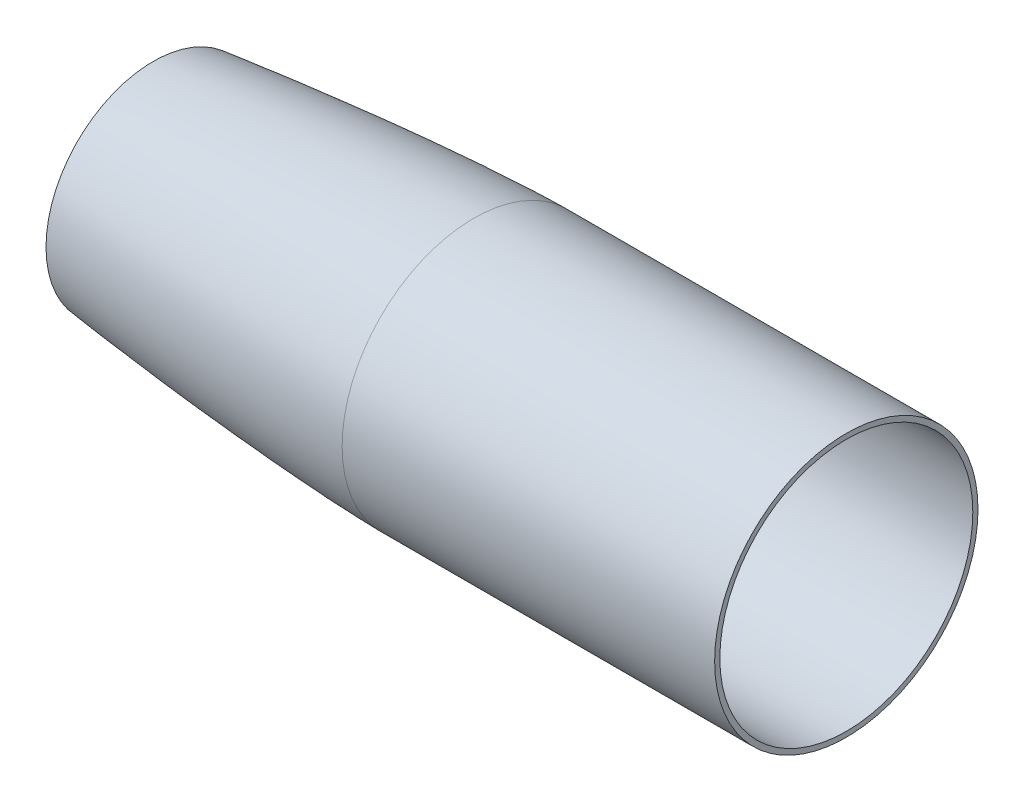
SolidWorks part; units mm, degrees
material "1060 Alloy"
ref_plane "Front Plane" through (0, 0, 0) normal (0, 0, 1) x (1, 0, 0)
ref_plane "Top Plane" through (0, 0, 0) normal (0, 1, 0) x (1, 0, 0)
ref_plane "Right Plane" through (0, 0, 0) normal (1, 0, 0) x (0, 0, -1)
sketch "Sketch2" plane through (0, 0, 0) normal (0, 0, 1) x (1, 0, 0)
  line L0 (0, 0) -> (5.418, 0)
  line L2 (0, 0) -> (553.8752, 0) construction
  line L3 (500, 76) -> (500, 73)
  line L4 (500, 76) -> (515, 76)
  line L5 (515, 76) -> (515, 73)
  line L6 (515, 73) -> (500, 73)
  spline S0 degree 4 poles (0, 0) (0.0035, 0.0138) (0.0132, 0.0403) (0.0421, 0.0896) (0.1033, 0.1748) (0.1957, 0.2791) (0.3129, 0.3945) (0.4445, 0.5113) (0.6264, 0.662) (0.9054, 0.8743) (1.3931, 1.2103) (2.2715, 1.7479) (3.8159, 2.5811) (6.6298, 3.9077) (11.7322, 5.9906) (20.2155, 8.9748) (31.7245, 12.4921) (45.6068, 16.2812) (64.6514, 21.0209) (87.6584, 26.2066) (114.7224, 31.7463) (145.854, 37.5379) (177.0669, 42.8718) (208.3451, 47.8072) (239.6781, 52.3812) (271.0588, 56.6152) (302.4822, 60.5197) (330.0118, 63.6484) (353.6316, 66.1189) (373.3295, 68.0301) (389.0964, 69.4668) (404.872, 70.8061) (418.6831, 71.887) (430.5264, 72.7427) (440.3994, 73.4044) (448.3, 73.9011) (455.2148, 74.3048) (461.1432, 74.6268) (466.0844, 74.8778) (470.0378, 75.0676) (476.0055, 75.3363) (481.7365, 75.5634) (487.2308, 75.7481) (492.4881, 75.8847) (495.117, 75.9403) (497.3706, 75.978) (498.8731, 75.9936) (499.6244, 76) (500, 76) knots 0 0 0 0 0 0.000112 0.000223 0.000447 0.000827 0.001207 0.00152 0.001832 0.002688 0.003968 0.006183 0.009943 0.016507 0.028468 0.049587 0.080772 0.111303 0.141834 0.204204 0.266574 0.328944 0.391314 0.453684 0.516055 0.578425 0.640795 0.703165 0.73435 0.765535 0.79672 0.827905 0.85909 0.874683 0.890275 0.905868 0.92146 0.929257 0.937053 0.944849 0.952645 0.976323 0.982242 0.988161 0.994081 0.99704 1 1 1 1 1 construction
  spline S1 degree 4 poles (0, 0) (0.0035, 0.0138) (0.0132, 0.0403) (0.0421, 0.0896) (0.1033, 0.1748) (0.1957, 0.2791) (0.3129, 0.3945) (0.4445, 0.5113) (0.6264, 0.662) (0.9054, 0.8743) (1.3931, 1.2103) (2.2715, 1.7479) (3.8159, 2.5811) (6.6298, 3.9077) (11.7322, 5.9906) (20.2155, 8.9748) (31.7245, 12.4921) (45.6068, 16.2812) (64.6514, 21.0209) (87.6584, 26.2066) (114.7224, 31.7463) (145.854, 37.5379) (177.0669, 42.8718) (208.3451, 47.8072) (239.6781, 52.3812) (271.0588, 56.6152) (302.4822, 60.5197) (330.0118, 63.6484) (353.6316, 66.1189) (373.3295, 68.0301) (389.0964, 69.4668) (404.872, 70.8061) (418.6831, 71.887) (430.5264, 72.7427) (440.3994, 73.4044) (448.3, 73.9011) (455.2148, 74.3048) (461.1432, 74.6268) (466.0844, 74.8778) (470.0378, 75.0676) (476.0055, 75.3363) (481.7365, 75.5634) (487.2308, 75.7481) (492.4881, 75.8847) (495.117, 75.9403) (497.3706, 75.978) (498.8731, 75.9936) (499.6244, 76) (500, 76) knots 0 0 0 0 0 0.000112 0.000223 0.000447 0.000827 0.001207 0.00152 0.001832 0.002688 0.003968 0.006183 0.009943 0.016507 0.028468 0.049587 0.080772 0.111303 0.141834 0.204204 0.266574 0.328944 0.391314 0.453684 0.516055 0.578425 0.640795 0.703165 0.73435 0.765535 0.79672 0.827905 0.85909 0.874683 0.890275 0.905868 0.92146 0.929257 0.937053 0.944849 0.952645 0.976323 0.982242 0.988161 0.994081 0.99704 1 1 1 1 1
  spline S2 degree 1 poles (2.4624, -1.7136) (500, 73) knots 0 0 1 1 construction
  spline S3 degree 3 poles (2.4624, -1.7136) (2.5424, -1.6494) (2.6933, -1.5376) (3.1212, -1.2489) (3.7179, -0.8906) (4.4652, -0.4814) (5.1076, -0.1526) (5.9378, 0.2562) (7.1091, 0.8017) (9.333, 1.7664) (12.3239, 2.9507) (15.9793, 4.2841) (19.6752, 5.5474) (24.6447, 7.1593) (30.9085, 9.0604) (38.4818, 11.2071) (48.6307, 13.9277) (61.3908, 17.1092) (76.7777, 20.6702) (92.2196, 24.0233) (107.7036, 27.204) (128.3941, 31.2449) (154.3275, 35.9654) (185.5307, 41.1907) (216.8002, 46.0288) (258.5666, 52.0059) (310.893, 58.6395) (363.3445, 64.1826) (405.3687, 67.8844) (431.6575, 69.8522) (452.6995, 71.1743) (468.4852, 72.0184) (481.6389, 72.5729) (490.8435, 72.8482) (495.4357, 72.9473) (498.062, 72.985) (499.352, 73) (500, 73) knots 0.0017 0.0017 0.0017 0.0017 0.002675 0.00365 0.0056 0.00755 0.009247 0.010222 0.013399 0.017299 0.025098 0.032897 0.040696 0.048495 0.064094 0.079692 0.095291 0.126488 0.157685 0.188881 0.220078 0.251275 0.313669 0.376063 0.438456 0.50085 0.625638 0.750425 0.812819 0.875213 0.906409 0.937606 0.968803 0.984402 0.992201 0.9961 1 1 1 1 only from (5.418, 0) to (500, 73)
  dimension "D2" = 15
  dimension "D1" = 3
revolve "Revolve1" add sketch "Sketch2" angle 360 about L2 region at (247.3654, 52.8678, 0) region at (507.5, 74.5, 0)
sketch "Sketch3" plane through (0, 0, 0) normal (0, 0, 1) x (1, 0, 0)
  line L1 (-30, -20) -> (30, -20)
  line L2 (-30, -20) -> (-30, 20)
  line L3 (-30, 20) -> (30, 20)
  line L4 (30, -20) -> (30, 20)
  line L5 (-30, -20) -> (30, 20) construction
  line L6 (-30, 20) -> (30, -20) construction
  point P0 (0, 0)
  dimension "D1" = 40
  dimension "D2" = 60
extrude "Cut-Extrude1" cut sketch "Sketch3" against normal through all and the other way through all
sketch "Sketch5" plane through (0, 0, 0) normal (0, 0, 1) x (1, 0, 0)
  line L0 (0, 0) -> (553.8752, 0) construction
  circle A0 centre (507.5, 0) radius 3
  dimension "D2" = 6
  dimension "D1" = 507.5
sketch "Sketch6" plane through (0, 0, 0) normal (0, 1, 0) x (1, 0, 0)
  line L0 (515, 0) -> (500, 0) construction
  circle A0 centre (507.5, 0) radius 3
  dimension "D1" = 6
sketch "Sketch7" plane through (0, 0, 0) normal (0, 0, 1) x (1, 0, 0)
  line L0 (244.6285, 0) -> (244.6285, 53)
  line L1 (0, 0) -> (553.8752, 0) construction
  line L2 (244.6285, 0) -> (244.6285, -63.9576)
  line L3 (244.6285, -63.9576) -> (36.3975, -63.9576)
  line L4 (36.3975, -63.9576) -> (36.3975, 53)
  line L5 (36.3975, 53) -> (244.6285, 53)
  line L7 (36.3975, -63.9576) -> (11.2418, -63.9576)
  line L8 (36.3975, -63.9576) -> (36.3975, 53)
  line L9 (36.3975, 53) -> (11.2418, 53)
  line L10 (11.2418, -63.9576) -> (11.2418, 53)
  spline S0 degree 4 poles (0, 0) (0.0035, 0.0138) (0.0132, 0.0403) (0.0421, 0.0896) (0.1033, 0.1748) (0.1957, 0.2791) (0.3129, 0.3945) (0.4445, 0.5113) (0.6264, 0.662) (0.9054, 0.8743) (1.3931, 1.2103) (2.2715, 1.7479) (3.8159, 2.5811) (6.6298, 3.9077) (11.7322, 5.9906) (20.2155, 8.9748) (31.7245, 12.4921) (45.6068, 16.2812) (64.6514, 21.0209) (87.6584, 26.2066) (114.7224, 31.7463) (145.854, 37.5379) (177.0669, 42.8718) (208.3451, 47.8072) (239.6781, 52.3812) (271.0588, 56.6152) (302.4822, 60.5197) (330.0118, 63.6484) (353.6316, 66.1189) (373.3295, 68.0301) (389.0964, 69.4668) (404.872, 70.8061) (418.6831, 71.887) (430.5264, 72.7427) (440.3994, 73.4044) (448.3, 73.9011) (455.2148, 74.3048) (461.1432, 74.6268) (466.0844, 74.8778) (470.0378, 75.0676) (476.0055, 75.3363) (481.7365, 75.5634) (487.2308, 75.7481) (492.4881, 75.8847) (495.117, 75.9403) (497.3706, 75.978) (498.8731, 75.9936) (499.6244, 76) (500, 76) knots 0 0 0 0 0 0.000112 0.000223 0.000447 0.000827 0.001207 0.00152 0.001832 0.002688 0.003968 0.006183 0.009943 0.016507 0.028468 0.049587 0.080772 0.111303 0.141834 0.204204 0.266574 0.328944 0.391314 0.453684 0.516055 0.578425 0.640795 0.703165 0.73435 0.765535 0.79672 0.827905 0.85909 0.874683 0.890275 0.905868 0.92146 0.929257 0.937053 0.944849 0.952645 0.976323 0.982242 0.988161 0.994081 0.99704 1 1 1 1 1 construction
  dimension "D1" = 53
extrude "Cut-Extrude4" cut sketch "Sketch7" against normal blind 200 and the other way blind 200 contours L10 L7 L4 L9 | L5 L4 L3 L2 L0 region at (140.513, -5.4788, 0) region at (23.8196, -5.4788, 0)
sketch "Sketch10" plane through (0, 0, 0) normal (0, 0, 1) x (1, 0, 0)
  line L0 (515, 0) -> (315, 0)
  line L1 (515, -76) -> (515, 76) construction
  line L2 (0, 0) -> (553.8752, 0) construction
  line L4 (315, 0) -> (233.2463, 0)
  line L5 (315, 0) -> (315, 71.8618)
  line L6 (315, 71.8618) -> (233.2463, 71.8618)
  line L7 (233.2463, 0) -> (233.2463, 71.8618)
  line L8 (315, 0) -> (233.2463, 0)
  line L9 (315, 0) -> (315, -66.1112)
  line L10 (315, -66.1112) -> (233.2463, -66.1112)
  line L11 (233.2463, 0) -> (233.2463, -66.1112)
  dimension "D1" = 200
extrude "Cut-Extrude5" cut sketch "Sketch10" against normal blind 200 and the other way blind 200 contours L7 L4 L5 L6 | L4 L11 L10 L9 region at (274.1232, -33.0556, 0) region at (274.1232, 35.9309, 0)
sketch "Sketch11" plane through (515, 0, 0) normal (1, 0, 0) x (0, 0, -1)
  line L0 (3, 0) -> (-3, 0) construction
  circle A0 centre (0, 0) radius 76
  circle A1 centre (0, 0) radius 73
extrude "Boss-Extrude1" add sketch "Sketch11" along normal blind 200
equation "\"Length\"= 500mm"
equation "\"Radius\"= 76mm"
equation "\"WallThickness\"= 3mm"
equation "\"D1@Sketch2\"= \"WallThickness\""
equation "\"tipOD\"= 40mm"
equation "\"tipLength\"= 30mm"
equation "\"D1@Sketch3\"= \"tipOD\""
equation "\"D2@Sketch3\"= \"tipLength\" * 2"
equation "\"MountingBoltDiameter\"= 6mm"
equation "\"D1@Sketch5\"= \"Length\" + 7.5mm"
equation "\"D2@Sketch5\"= \"MountingBoltDiameter\""
equation "\"D1@Sketch6\"= \"MountingBoltDiameter\""
